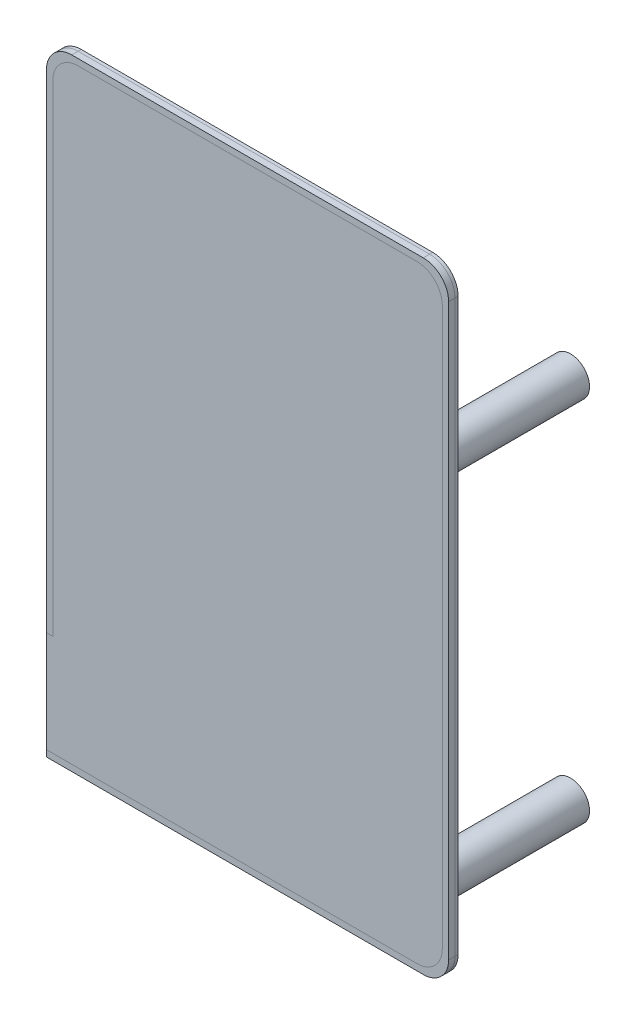
SolidWorks part; units mm, degrees
ref_plane "Front Plane" through (0, 0, 0) normal (1, 0, 0) x (0, 1, 0)
ref_plane "Top Plane" through (0, 0, 0) normal (0, 0, 1) x (0, 1, 0)
ref_plane "Right Plane" through (0, 0, 0) normal (0, 1, 0) x (-1, 0, 0)
sketch "Sketch1" plane through (0, 0, 0) normal (0, 0, 1) x (0, 1, 0)
  line L0 (58.5356, -40.316) -> (-31.4644, -40.316) construction
  line L1 (-35.4644, 23.184) -> (62.5356, 23.184)
  line L2 (-35.4644, 23.184) -> (-35.4644, -40.316)
  line L3 (-35.4644, -40.316) -> (62.5356, -40.316)
  line L4 (62.5356, 23.184) -> (62.5356, -40.316)
  line L5 (62.5356, 19.184) -> (62.5356, -36.316) construction
  line L6 (-33.7644, 21.484) -> (-33.7644, 21.684) construction
  line L7 (-33.7644, 21.484) -> (60.8356, 21.484)
  line L8 (-33.7644, 21.484) -> (-33.7644, -38.616)
  line L9 (-33.7644, -38.616) -> (60.8356, -38.616)
  line L10 (60.8356, 21.484) -> (60.8356, -38.616)
  line L11 (-32.2644, 19.984) -> (59.3356, 19.984)
  line L12 (-32.2644, 19.984) -> (-32.2644, -37.116)
  line L13 (-32.2644, -37.116) -> (59.3356, -37.116)
  line L14 (59.3356, 19.984) -> (59.3356, -37.116)
  line L15 (-33.9644, 23.184) -> (-33.9644, -34.816) construction
  line L16 (-33.9644, 21.484) -> (-33.7644, 21.484) construction
  line L17 (61.0356, -34.816) -> (60.8356, -34.816) construction
  line L18 (57.0356, -38.816) -> (57.0356, -38.616) construction
  line L19 (-29.9644, -38.816) -> (57.0356, -38.816) construction
  line L20 (-32.2644, 19.984) -> (-33.7644, 19.984) construction
  line L21 (-32.2644, 19.984) -> (-32.2644, 21.484) construction
  line L22 (-33.9644, 21.684) -> (-18.9644, 21.684) construction
  line L23 (59.3356, -37.116) -> (59.3356, -38.616) construction
  line L24 (59.3356, -37.116) -> (60.8356, -37.116) construction
  circle A0 centre (-26.4644, 15.934) radius 0.95
  circle A1 centre (-26.4644, 15.934) radius 3
  circle A2 centre (31.5356, 15.934) radius 0.95
  circle A3 centre (31.5356, 15.934) radius 3
  circle A4 centre (31.5356, -33.066) radius 0.95
  circle A5 centre (31.5356, -33.066) radius 3
  circle A6 centre (-26.4644, -33.066) radius 0.95
  circle A7 centre (-26.4644, -33.066) radius 3
  circle A8 centre (-26.4644, 15.934) radius 0.95 construction
  circle A9 centre (-26.4644, 15.934) radius 3 construction
  dimension "D1" = 0.2
  dimension "D2" = 1.5
extrude "Boss-Extrude1" add sketch "Sketch1" along normal blind 1.5 contours L1 L4 L3 L2
extrude "Boss-Extrude2" add sketch "Sketch1<3>" against normal blind 1.5 from surface contours L10 L7 L8 L9 L11 L14 L13 L12 region at (-20.3633, 13.5356, 0) starting at face at (8.566, 13.5356, 0)
sketch "Sketch1<3>" plane through (0, 0, 0) normal (0, 0, 1) x (0, 1, 0) same geometry as "Sketch1"
extrude "Boss-Extrude3" add sketch "Sketch1<5>" against normal offset from surface (25 mm away) 1.5 from surface contours A5 A4 | A3 A2 | A1 A0 | A7 A6 region at (-15.934, -29.3795, 0) region at (-15.934, 28.6205, 0) region at (33.066, 28.6205, 0) region at (33.066, -29.3795, 0) starting at face at (8.566, 13.5356, 0)
sketch "Sketch1<5>" plane through (0, 0, 0) normal (0, 0, 1) x (0, 1, 0) same geometry as "Sketch1"
sketch "Sketch3" plane through (0, 0, 1.5) normal (0, 0, 1) x (1, 0, 0)
  line L0 (-23.184, 62.5356) -> (40.316, 62.5356)
  line L1 (40.316, 62.5356) -> (40.316, -35.4644)
  line L2 (40.316, -35.4644) -> (-23.184, -35.4644)
  line L3 (-23.184, -35.4644) -> (-23.184, 62.5356)
  line L4 (-22.184, 61.5356) -> (39.316, 61.5356)
  line L5 (39.316, 61.5356) -> (39.316, -34.4644)
  line L6 (39.316, -34.4644) -> (-22.184, -34.4644)
  line L7 (-22.184, -34.4644) -> (-22.184, 61.5356)
  line L8 (-22.184, 61.5356) -> (-23.184, 61.5356) construction
  line L9 (-22.184, 61.5356) -> (-22.184, 62.5356) construction
  line L10 (39.316, -34.4644) -> (40.316, -34.4644) construction
  line L11 (39.316, -34.4644) -> (39.316, -35.4644) construction
  line L12 (-22.184, -34.4644) -> (-23.184, -34.4644)
  line L13 (-23.184, -18.4644) -> (-22.184, -18.4644)
  line L14 (-23.184, -18.4644) -> (-24.684, -18.4644) construction
  line M13 (-23.184, -35.4644) -> (40.316, -35.4644)
  line M14 (40.316, -35.4644) -> (40.316, 62.5356)
  line M15 (40.316, 62.5356) -> (-23.184, 62.5356)
  line M16 (-23.184, 62.5356) -> (-23.184, -35.4644)
  dimension "D1" = 1
extrude "Cut-Extrude1" cut sketch "Sketch3" against normal blind 1 contours L11 L6 L7 L8 L3 M13 region at (8.566, 62.4189, 1.5)
fillet "Fillet1" radius 4 12 edges at (39.316, 61.5356, 1) (40.316, 62.5356, 0.25) (38.616, 60.8356, -0.75) (39.316, -34.4644, 1) (40.316, -35.4644, 0.25) (38.616, -33.7644, -0.75) (-21.484, 60.8356, -0.75) (-23.184, 62.5356, 0.25) (-22.184, 61.5356, 1) (37.116, -32.2644, -0.75) (37.116, 59.3356, -0.75) (-19.984, 59.3356, -0.75)
extrude "Boss-Extrude4" add sketch "Sketch3<3>" against normal up to surface (1 mm away) separate body contours L13 L7 L4 L5 L6 L12 L3 M16 M13 M14 M15 region at (8.566, 62.4189, 1.5) up to face at (8.107, 15.2017, 0.5)
sketch "Sketch3<3>" plane through (0, 0, 1.5) normal (0, 0, 1) x (1, 0, 0) same geometry as "Sketch3"
fillet "Fillet2" radius 4 6 edges at (40.316, 62.5356, 1) (39.316, 61.5356, 1) (-23.184, 62.5356, 1) (-22.184, 61.5356, 1) (39.316, -34.4644, 1) (40.316, -35.4644, 1)
